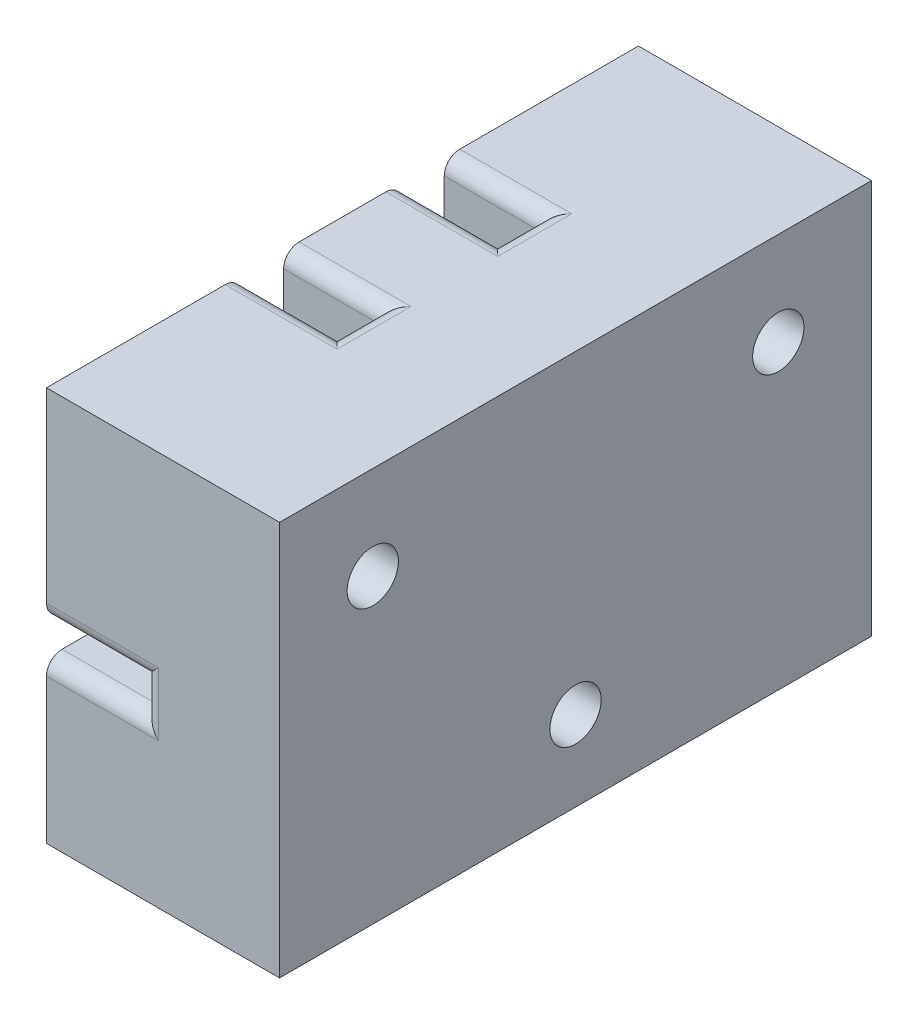
SolidWorks part; units mm, degrees
ref_plane "Front Plane" through (0, 0, 0) normal (0, 0, 1) x (1, 0, 0)
ref_plane "Top Plane" through (0, 0, 0) normal (0, 1, 0) x (1, 0, 0)
ref_plane "Right Plane" through (0, 0, 0) normal (1, 0, 0) x (0, 0, -1)
sketch "Sketch1" plane through (0, 0, 0) normal (1, 0, 0) x (0, 0, -1)
  line L0 (0, 25.4) -> (38.1, 25.4) construction
  line L5 (0, 12.395) -> (12.5, 12.395)
  line L6 (12.5, 12.395) -> (12.5, 25.4)
  line L7 (12.5, 25.4) -> (15.26, 25.4)
  line L8 (15.26, 25.4) -> (15.26, 10.325)
  line L9 (15.26, 10.325) -> (0, 10.325)
  line L10 (0, 10.325) -> (0, 12.395)
  line L11 (0, 11.36) -> (15.26, 11.36) construction
  line L12 (19.05, 0) -> (19.05, 25.4) construction
  line L13 (13.88, 25.4) -> (13.88, 10.325) construction
  line L14 (22.84, 10.325) -> (38.1, 10.325)
  line L15 (22.84, 25.4) -> (22.84, 10.325)
  line L16 (25.6, 25.4) -> (22.84, 25.4)
  line L17 (25.6, 12.395) -> (25.6, 25.4)
  line L18 (38.1, 12.395) -> (25.6, 12.395)
  line L19 (38.1, 10.325) -> (38.1, 12.395)
  line L20 (0, 25.4) -> (38.1, 25.4)
  line L21 (0, 25.4) -> (0, 0)
  line L22 (0, 0) -> (38.1, 0)
  line L23 (38.1, 25.4) -> (38.1, 0)
  line L24 (0, 10.325) -> (0, 0)
  line L25 (0, 10.325) -> (0, 0) construction
  line L26 (0, 10.325) -> (38.1, 0) construction
  line L27 (0, 0) -> (38.1, 10.325) construction
  circle A0 centre (19.05, 5.1625) radius 1.65
  circle A1 centre (6, 19.4) radius 1.65
  circle A2 centre (32.1, 19.4) radius 1.65
  dimension "D8" = 3.3
  dimension "D5" = 12.5
  dimension "D1" = 25.4
  dimension "D7" = 38.1
  dimension "D2" = 2.07
  dimension "D3" = 2.76
  dimension "D4" = 15.26
  dimension "D6" = 11.36
  dimension "D9" = 6
  dimension "D10" = 6
extrude "Boss-Extrude2" add sketch "Sketch1" along normal blind 15 contours L20 L21 L5 L6 | L23 L20 L17 L18 | L14 L19 L18 L17 L16 L15 | L23 L14 L15 L20 L8 L9 L21 L22 | L6 L7 L8 L9 L10 L5 region at (0, 18.8975, -0.1804) region at (0, 8.0702, -19.05) region at (0, 25.1855, -24.22) region at (0, 25.2196, -31.85)
extrude "Cut-Extrude1" cut sketch "Sketch1<9>" along normal blind 6.2 contours L14 L19 L18 L17 L16 L15 | L8 L9 L10 L5 L6 L7 region at (0, 25.1855, -24.22)
sketch "Sketch1<9>" plane through (0, 0, 0) normal (1, 0, 0) x (0, 0, -1) same geometry as "Sketch1"
fillet "Fillet1" radius 1 16 edges at (6.2, 25.4, -24.22) (6.2, 25.4, -13.88) (6.2, 11.36, -38.1) (6.2, 11.36, 0) (3.1, 25.4, -25.6) (3.1, 25.4, -22.84) (3.1, 25.4, -12.5) (3.1, 25.4, -15.26) (3.1, 10.325, 0) (3.1, 12.395, 0) (3.1, 12.395, -12.5) (3.1, 10.325, -15.26) (3.1, 10.325, -22.84) (3.1, 12.395, -25.6) (3.1, 10.325, -38.1) (3.1, 12.395, -38.1)
equation "\"Ø Smaller Shaft\"=6.35"
equation "\"Shaft Distance\"= 25.4"
equation "\"Width\"= \"Ø Smaller Shaft\" * 2 + \"Shaft Distance\" + \"Width End\" * 2"
equation "\"Width End\"= 6.35"
equation "\"Length\"= 38.1"
equation "\"Rod to Belt\"= 31.75 + 3"
equation "\"Nom Tolerance\"= 0.15"
equation "\"Belt\"= 6"
equation "\"Belt Thickness\"=1.38"
equation "\"Ø Pulley\"= 10.9"
equation "\"Pully Distance\"= 35"
equation "\"Ø Outer Washer\"= 12.7"
equation "\"Washer Thickness\"=2"
equation "\"D1@Sketch1\"=\"Width\"/2"
equation "\"D7@Sketch1\"=\"Length\""
equation "\"D2@Sketch1\"=\"Belt Thickness\"*1.5"
equation "\"D3@Sketch1\"=\"Belt Thickness\"*2"
equation "\"D1@Cut-Extrude1\"= \"Belt\" + 0.2"
equation "\"D6@Sketch1\"=(\"Pully Distance\"/2)-(\"Ø Pulley\"/2)-(\"Belt Thickness\"/2)"
equation "\"M3 Screw Size\"= 3"
equation "\"D8@Sketch1\"= \"M3 Screw Size\" + \"Nom Tolerance\"*2"
